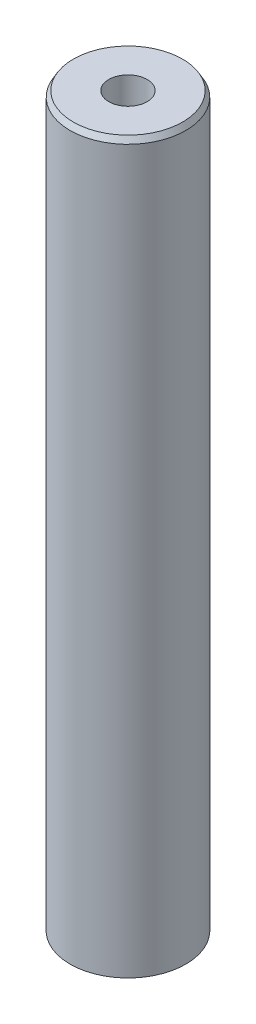
SolidWorks part; units mm, degrees
ref_plane "Front Plane" through (0, 0, 0) normal (0, 0, 1) x (1, 0, 0)
ref_plane "Top Plane" through (0, 0, 0) normal (0, 1, 0) x (1, 0, 0)
ref_plane "Right Plane" through (0, 0, 0) normal (1, 0, 0) x (0, 0, -1)
sketch "Sketch1" plane through (0, 0, 0) normal (0, 1, 0) x (1, 0, 0)
  circle A0 centre (0, 0) radius 47.5
  dimension "SHAFT_OD" = 95
extrude "Boss-Extrude1" add sketch "Sketch1" along normal blind 600
sketch "Sketch2" plane through (0, 0, 0) normal (0, 1, 0) x (1, 0, 0)
  circle A0 centre (0, 0) radius 15.7943
  dimension "BORE_D" = 31.5886
extrude "Cut-Extrude1" cut sketch "Sketch2" along normal through all
chamfer "Chamfer1" distance 4.6337 angle 30 2 edges at (0, 600, 47.5) (0, 0, 47.5) first distance on face at (0, 600, 47.5) first distance on face at (0, 0, 15.7943)
